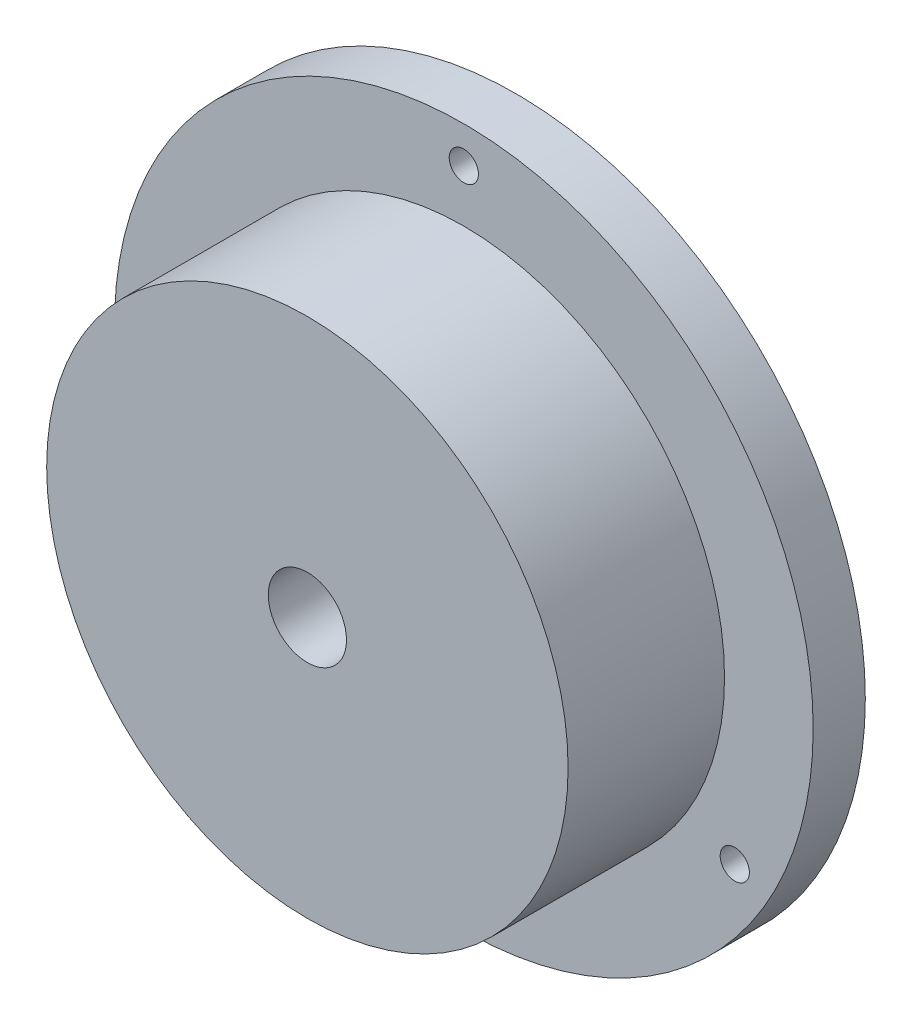
SolidWorks part; units mm, degrees
ref_plane "Front Plane" through (0, 0, 0) normal (0, 0, 1) x (1, 0, 0)
ref_plane "Top Plane" through (0, 0, 0) normal (0, 1, 0) x (1, 0, 0)
ref_plane "Right Plane" through (0, 0, 0) normal (1, 0, 0) x (0, 0, -1)
sketch "Sketch1" plane through (0, 0, 0) normal (0, 0, 1) x (1, 0, 0)
  circle A0 centre (0, 0) radius 21.2725
  dimension "D1" = 42.545
extrude "Boss-Extrude1" add sketch "Sketch1" along normal blind 3.175
sketch "Sketch2" plane through (0, 0, 3.175) normal (0, 0, 1) x (1, 0, 0)
  circle A0 centre (0, 0) radius 15.875
  dimension "D1" = 31.75
extrude "Boss-Extrude2" add sketch "Sketch2" along normal blind 9.525
hole_wizard "3/16 (0.1875) Diameter Hole1" positions "Sketch4" profile "Sketch3" hole size "3/16" standard "Ansi Inch" end condition through all
sketch "Sketch4" plane through (0, 0, 12.7) normal (0, 0, 1) x (1, 0, 0)
  point P1 (0, 0)
sketch "Sketch3" plane through (0, 0, 12.7) normal (1, 0, 0) x (0, -1, 0)
  line L0 (0, 0) -> (0, 12.7)
  line L1 (0, 12.7) -> (2.3812, 12.7)
  line L2 (2.3812, 12.7) -> (2.3812, 0)
  line L5 (2.3812, 0) -> (0, 0)
  line L11 (0, -6.35) -> (0, 107.95) construction
  dimension "Thru Hole Dia." = 4.7625
  dimension "Thru Hole Depth" = 12.7
hole_wizard "#2-56 Tapped Hole3" positions "Sketch10" profile "Sketch9" tap size "#2-56" standard "Ansi Inch" end condition through all
sketch "Sketch10" plane through (0, 0, 3.175) normal (0, 0, 1) x (1, 0, 0)
  point P1 (0, 19.05)
  dimension "D1" = 19.05
sketch "Sketch9" plane through (0, 19.05, 3.175) normal (1, 0, 0) x (0, -1, 0)
  line L0 (0, 0) -> (0, 3.175)
  line L1 (0, 3.175) -> (0.889, 3.175)
  line L2 (0.889, 3.175) -> (0.889, 0)
  line L5 (0.889, 0) -> (0, 0)
  line L11 (0, -6.35) -> (0, 107.95) construction
  dimension "Thread Major Dia." = 1.778
  dimension "Thru Tap Drill Depth" = 3.175
pattern_circular "CirPattern1" count 3 every 120 about axis through (0, 0, 3.175) along (0, 0, 1) of "#2-56 Tapped Hole3"
sketch "Sketch11" plane through (0, 0, 0) normal (0, 0, -1) x (-1, 0, 0)
  line L0 (0, 0) -> (0, -21.2725) construction
  circle A1 centre (0, 0) radius 21.2725 construction
ref_plane "Plane1" through (0, -21.2725, 0) normal (0, -1, 0) x (1, 0, 0)
hole_wizard "#8-32 Tapped Hole1" positions "Sketch13" profile "Sketch12" tap size "#8-32" standard "Ansi Inch"
sketch "Sketch13" plane through (0, -21.2725, 0) normal (0, -1, 0) x (1, 0, 0)
  line L0 (-21.2725, 0) -> (21.2725, 0) construction
  point P1 (0, 7.9248)
  dimension "D1" = 7.9248
sketch "Sketch12" plane through (0, -21.2725, 7.9248) normal (1, 0, 0) x (0, 0, -1)
  line L0 (0, 0) -> (0, 22.3093)
  line L1 (0, 22.3093) -> (1.7272, 21.2715)
  line L2 (1.7272, 21.2715) -> (1.7272, 0)
  line L5 (1.7272, 0) -> (0, 0)
  line L10 (0, 22.3093) -> (-1.7272, 21.2715) construction
  line L11 (0, -6.35) -> (0, 107.95) construction
  dimension "Tap Drill Dia." = 3.4544
  dimension "Tap Drill Depth" = 21.2715
  dimension "Drill Angle" = 118
